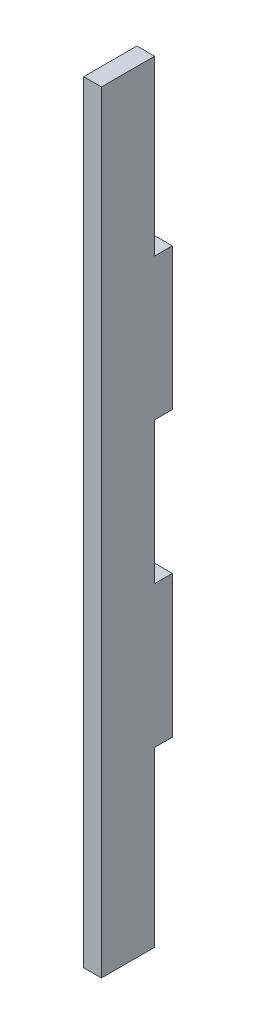
SolidWorks part; units mm, degrees
material "Acrylic (Medium-high impact)"
ref_plane "Front" through (0, 0, 0) normal (0, 0, 1) x (1, 0, 0)
ref_plane "Top" through (0, 0, 0) normal (0, 1, 0) x (1, 0, 0)
ref_plane "Right" through (0, 0, 0) normal (1, 0, 0) x (0, 0, -1)
sketch "Sketch1" plane through (0, 0, 0) normal (1, 0, 0) x (0, 0, -1)
  line L3 (-6.35, -132.588) -> (6.35, -132.588)
  line L69 (6.35, 0) -> (6.35, -132.588)
  line L70 (-6.35, -132.588) -> (-6.35, 0)
  line L71 (-6.35, -127) -> (6.35, -127) construction
  line L74 (4.7625, -25.4) -> (4.7625, -50.8) construction
  line L75 (4.7625, -76.2) -> (4.7625, -101.6) construction
  line L82 (6.35, 0) -> (-6.35, 0)
  line L83 (6.35, 0) -> (6.35, -25.4)
  line L84 (6.35, 0) -> (3.175, 0)
  line L85 (3.175, 0) -> (3.175, -25.4)
  line L86 (6.35, -25.4) -> (3.175, -25.4)
  line L87 (6.35, -50.8) -> (6.35, -76.2)
  line L88 (6.35, -50.8) -> (3.175, -50.8)
  line L89 (3.175, -50.8) -> (3.175, -76.2)
  line L90 (6.35, -76.2) -> (3.175, -76.2)
  line L96 (6.35, -101.6) -> (3.175, -101.6)
  line L97 (6.35, -101.6) -> (6.35, -127)
  line L98 (6.35, -127) -> (3.175, -127)
  line L99 (3.175, -101.6) -> (3.175, -127)
  line L101 (6.35, -127) -> (3.175, -127)
  line L102 (6.35, -127) -> (6.35, -132.588)
  line L103 (6.35, -132.588) -> (3.175, -132.588)
  line L104 (3.175, -127) -> (3.175, -132.588)
  line L106 (-6.35, 0) -> (3.175, 0)
  line L107 (-6.35, 0) -> (-6.35, 5.588)
  line L108 (-6.35, 5.588) -> (3.175, 5.588)
  line L109 (3.175, 0) -> (3.175, 5.588)
  point P4 (0, -132.588)
  dimension "D2" = 25.4
  dimension "D4" = 3.175
  dimension "D1" = 25.4
  dimension "D5" = 9.525
  dimension "D3" = 5.588
extrude "Boss-Extrude1" add sketch "Sketch1" along normal blind 3.175
sketch "Sketch2" [suppressed] plane through (3.175, 0, 0) normal (1, 0, 0) x (0, 0, -1)
  line L6 (6.35, -70.0024) -> (18.542, -70.0024)
  line L7 (6.35, -70.0024) -> (6.35, -85.9536)
  line L8 (6.35, -85.9536) -> (18.542, -85.9536)
  line L9 (18.542, -70.0024) -> (18.542, -85.9536)
  line L11 (6.35, -76.3905) -> (12.192, -76.3905)
  line L12 (6.35, -76.3905) -> (6.35, -79.5655)
  line L13 (6.35, -79.5655) -> (12.192, -79.5655)
  line L14 (12.192, -76.3905) -> (12.192, -79.5655)
  line L31 (6.35, -70.0024) -> (3.175, -70.0024) construction
  point P22 (12.192, -77.978)
  point P27 (18.542, -77.978)
  dimension "D1" = 12.192
  dimension "D3" = 3.175
  dimension "D4" = 5.842
extrude "Boss-Extrude2" [suppressed] add sketch "Sketch2" against normal up to surface (2.9972 mm away) up to face at (0, -63.5, -2.6458)
equation "\"bottomThickness\"= .220in"
equation "\"wallThickness\"= .125in"
equation "\"D4@Sketch1\"=\"wallThickness\""
equation "\"D1@Boss-Extrude1\"=\"wallThickness\""
equation "\"D3@Sketch1\"=\"bottomThickness\""
